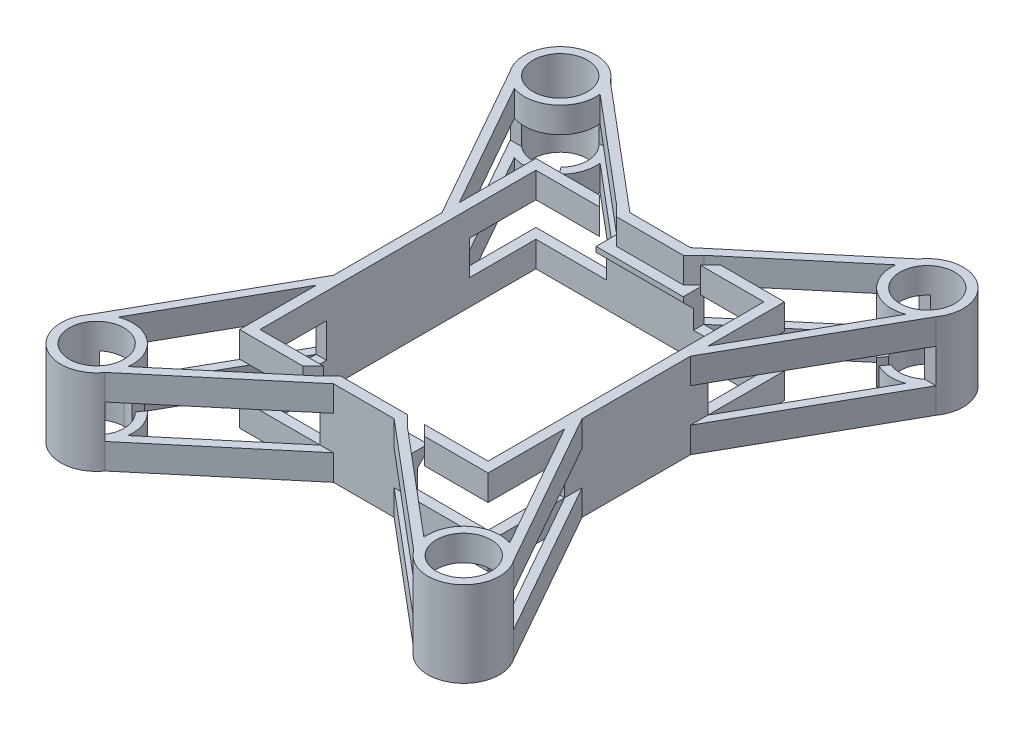
SolidWorks part; units mm, degrees
ref_plane "Front Plane" through (0, 0, 0) normal (0, 0, 1) x (1, 0, 0)
ref_plane "Top Plane" through (0, 0, 0) normal (0, 1, 0) x (1, 0, 0)
ref_plane "Right Plane" through (0, 0, 0) normal (1, 0, 0) x (0, 0, -1)
sketch "Sketch1" plane through (0, 0, 0) normal (0, 1, 0) x (1, 0, 0)
  line L0 (-24.0396, 23.0747) -> (-14.5922, 23.0747)
  line L1 (-22.8396, 21.8747) -> (3.8604, 21.8747)
  line L2 (-22.8396, 21.8747) -> (-22.8396, -10.4253)
  line L3 (-22.8396, -10.4253) -> (3.8604, -10.4253)
  line L4 (3.8604, 21.8747) -> (3.8604, -10.4253)
  line L5 (5.0604, 23.0747) -> (5.0604, 14.1087)
  line L6 (-24.0396, -11.6253) -> (-14.5922, -11.6253)
  line L7 (-24.0396, 23.0747) -> (-24.0396, 14.1087)
  line L8 (-32.3963, 28.911) -> (-24.0396, 14.1087)
  line L9 (-26.8082, 33.3597) -> (-14.5922, 23.0747)
  line L10 (-34.4055, 30.4359) -> (-24.0396, 12.0747)
  line L11 (-27.5525, 35.2935) -> (-13.0396, 23.0747)
  line L12 (-33.5347, 30.9275) -> (-23.1688, 12.5663) construction
  line L13 (-28.1965, 34.5285) -> (-13.6836, 22.3097) construction
  line L14 (-24.0396, 12.0747) -> (-24.0396, -0.6253)
  line L15 (-24.0396, 23.0747) -> (-24.0396, -11.6253) construction
  line L16 (-13.0396, 23.0747) -> (-5.9396, 23.0747)
  line L17 (-24.0396, 23.0747) -> (5.0604, 23.0747) construction
  line L18 (-9.4896, 43.1002) -> (-9.4896, -24.274) construction
  line L19 (-35.8782, 5.7247) -> (17.7365, 5.7247) construction
  line L20 (8.5733, 35.2935) -> (-5.9396, 23.0747)
  line L21 (7.8291, 33.3597) -> (-4.3869, 23.0747)
  line L22 (15.4263, 30.4359) -> (5.0604, 12.0747)
  line L23 (13.4171, 28.911) -> (5.0604, 14.1087)
  line L24 (-27.5525, -23.8442) -> (-13.0396, -11.6253)
  line L25 (-26.8082, -21.9104) -> (-14.5922, -11.6253)
  line L26 (-34.4055, -18.9866) -> (-24.0396, -0.6253)
  line L27 (-32.3963, -17.4617) -> (-24.0396, -2.6594)
  line L28 (8.5733, -23.8442) -> (-5.9396, -11.6253)
  line L29 (7.8291, -21.9104) -> (-4.3869, -11.6253)
  line L30 (13.4171, -17.4617) -> (5.0604, -2.6594)
  line L31 (15.4263, -18.9866) -> (5.0604, -0.6253)
  line L32 (-4.3869, 23.0747) -> (5.0604, 23.0747)
  line L33 (5.0604, 12.0747) -> (5.0604, -0.6253)
  line L34 (5.0604, 23.0747) -> (5.0604, -11.6253) construction
  line L35 (5.0604, -2.6594) -> (5.0604, -11.6253)
  line L36 (-4.3869, -11.6253) -> (5.0604, -11.6253)
  line L37 (-24.0396, -11.6253) -> (5.0604, -11.6253) construction
  line L38 (-13.0396, -11.6253) -> (-5.9396, -11.6253)
  line L39 (-24.0396, -2.6594) -> (-24.0396, -11.6253)
  circle A0 centre (-30.979, 32.8647) radius 3.2
  arc A1 (-27.5525, 35.2935) -> (-34.4055, 30.4359) centre (-30.979, 32.8647) ccw
  circle A2 centre (-30.979, 32.8647) radius 4.2 construction
  arc A3 (-32.3963, 28.911) -> (-26.8082, 33.3597) centre (-30.979, 32.8647) ccw
  arc A4 (13.4171, 28.911) -> (7.8291, 33.3597) centre (11.9998, 32.8647) cw
  arc A5 (8.5733, 35.2935) -> (15.4263, 30.4359) centre (11.9998, 32.8647) cw
  circle A6 centre (11.9998, 32.8647) radius 3.2
  arc A7 (-32.3963, -17.4617) -> (-26.8082, -21.9104) centre (-30.979, -21.4154) cw
  arc A8 (-27.5525, -23.8442) -> (-34.4055, -18.9866) centre (-30.979, -21.4154) cw
  circle A9 centre (-30.979, -21.4154) radius 3.2
  circle A10 centre (11.9998, -21.4154) radius 3.2
  arc A11 (8.5733, -23.8442) -> (15.4263, -18.9866) centre (11.9998, -21.4154) ccw
  arc A12 (13.4171, -17.4617) -> (7.8291, -21.9104) centre (11.9998, -21.4154) ccw
  point P8 (-13.0396, 23.0747)
  point P9 (-24.0396, 12.0747)
  point P17 (-30.979, 32.8647)
  point P42 (11.9998, 32.8647)
  point P54 (-30.979, -21.4154)
  point P65 (11.9998, -21.4154)
  dimension "D6" = 6.4
  dimension "D1" = 26.7
  dimension "D2" = 32.3
  dimension "D4" = 11
  dimension "D5" = 11
  dimension "D8" = 1
  dimension "D9" = 1
  dimension "D10" = 12
  dimension "D3" = 1.2
  dimension "D7" = 1
extrude "Boss-Extrude2" add sketch "Sketch1" along normal blind 10
ref_plane "Plane1" through (20, 0, 0) normal (1, 0, 0) x (0, 0, -1)
sketch "Sketch2" plane through (20, 0, 0) normal (1, 0, 0) x (0, 0, -1)
  line L1 (-18.9866, 10) -> (-18.9866, 0) construction
  line L2 (-0.6253, 10) -> (-0.6253, 0) construction
  line L3 (5.7247, -5.597) -> (5.7247, 19.988) construction
  line L5 (-18.9866, 5) -> (-18.9866, 7)
  line L6 (-18.9866, 7) -> (-0.6253, 7)
  line L7 (-0.6253, 5) -> (-0.6253, 7)
  line L9 (-18.9866, 5) -> (-18.9866, 3)
  line L10 (-18.9866, 3) -> (-0.6253, 3)
  line L11 (-0.6253, 5) -> (-0.6253, 3)
  line L12 (30.4359, 7) -> (12.0747, 7)
  line L13 (12.0747, 5) -> (12.0747, 7)
  line L15 (30.4359, 5) -> (30.4359, 7)
  line L16 (30.4359, 3) -> (12.0747, 3)
  line L17 (12.0747, 5) -> (12.0747, 3)
  line L19 (30.4359, 5) -> (30.4359, 3)
  dimension "D1" = 2
  dimension "D2" = 2
extrude "Cut-Extrude1" cut sketch "Sketch2" against normal through all
ref_plane "Plane2" through (0, 0, 30) normal (0, 0, 1) x (1, 0, 0)
sketch "Sketch3" plane through (0, 0, 30) normal (0, 0, 1) x (1, 0, 0)
  line L0 (-27.5525, 10) -> (-27.5525, 0) construction
  line L1 (-27.5525, 7) -> (8.5733, 7)
  line L2 (-27.5525, 7) -> (-27.5525, 3)
  line L3 (-27.5525, 3) -> (8.5733, 3)
  line L4 (8.5733, 7) -> (8.5733, 3)
  line L5 (8.5733, 10) -> (8.5733, 0) construction
extrude "Cut-Extrude2" cut sketch "Sketch3" against normal through all
sketch "Sketch4" plane through (-27.5525, 0, 0) normal (1, 0, 0) x (0, 0, -1)
  line L1 (-23.8442, 7) -> (-18.9866, 7)
  line L2 (-23.8442, 7) -> (-23.8442, 3)
  line L3 (-23.8442, 3) -> (-18.9866, 3)
  line L4 (-18.9866, 7) -> (-18.9866, 3)
extrude "Cut-Extrude3" cut sketch "Sketch4" against normal up to surface (1.343 mm away) up to face at (-30.979, 5, 18.601)
sketch "Sketch5" plane through (8.5733, 0, 0) normal (-1, 0, 0) x (0, 0, 1)
  line L1 (23.8442, 3) -> (18.9866, 3)
  line L2 (23.8442, 3) -> (23.8442, 7)
  line L3 (23.8442, 7) -> (18.9866, 7)
  line L4 (18.9866, 3) -> (18.9866, 7)
extrude "Cut-Extrude4" cut sketch "Sketch5" against normal up to surface (1.343 mm away) up to face at (11.9998, 5, 18.601)
sketch "Sketch6" plane through (-27.5525, 0, 0) normal (1, 0, 0) x (0, 0, -1)
  line L1 (35.2935, 3) -> (30.4359, 3)
  line L2 (35.2935, 3) -> (35.2935, 7)
  line L3 (35.2935, 7) -> (30.4359, 7)
  line L4 (30.4359, 3) -> (30.4359, 7)
extrude "Cut-Extrude5" cut sketch "Sketch6" against normal up to surface (1.343 mm away) up to face at (-30.979, 5, -30.0503)
sketch "Sketch7" plane through (8.5733, 0, 0) normal (-1, 0, 0) x (0, 0, 1)
  line L1 (-35.2935, 7) -> (-30.4359, 7)
  line L2 (-35.2935, 7) -> (-35.2935, 3)
  line L3 (-35.2935, 3) -> (-30.4359, 3)
  line L4 (-30.4359, 7) -> (-30.4359, 3)
extrude "Cut-Extrude6" cut sketch "Sketch7" against normal up to surface (1.343 mm away) up to face at (11.9998, 5, -30.0503)
sketch "Sketch8" plane through (0, 3, 0) normal (0, 1, 0) x (1, 0, 0)
  line L0 (3.8604, 21.8747) -> (-22.8396, 21.8747) construction
  line L1 (-14.5922, 23.0747) -> (-4.3869, 23.0747)
  line L2 (-14.5922, 23.0747) -> (-14.5922, 21.8747)
  line L3 (-14.5922, 21.8747) -> (-4.3869, 21.8747)
  line L4 (-4.3869, 23.0747) -> (-4.3869, 21.8747)
  line L5 (-22.8396, -10.4253) -> (3.8604, -10.4253) construction
  line L6 (-14.5922, -11.6253) -> (-4.3869, -11.6253)
  line L7 (-14.5922, -11.6253) -> (-14.5922, -10.4253)
  line L8 (-14.5922, -10.4253) -> (-4.3869, -10.4253)
  line L9 (-4.3869, -11.6253) -> (-4.3869, -10.4253)
  line L10 (-22.8396, 21.8747) -> (-22.8396, -10.4253) construction
  line L11 (-24.0396, 14.1087) -> (-22.8396, 14.1087)
  line L12 (-24.0396, 14.1087) -> (-24.0396, -2.6594)
  line L13 (-24.0396, -2.6594) -> (-22.8396, -2.6594)
  line L14 (-22.8396, 14.1087) -> (-22.8396, -2.6594)
  line L15 (3.8604, -10.4253) -> (3.8604, 21.8747) construction
  line L16 (5.0604, 14.1087) -> (3.8604, 14.1087)
  line L17 (5.0604, 14.1087) -> (5.0604, -2.6594)
  line L18 (5.0604, -2.6594) -> (3.8604, -2.6594)
  line L19 (3.8604, 14.1087) -> (3.8604, -2.6594)
extrude "Boss-Extrude3" add sketch "Sketch8" along normal up to surface (4 mm away) up to face at (-9.4896, 7, -5.7247)
sketch "Sketch9" plane through (0, 3, 0) normal (0, 1, 0) x (1, 0, 0)
  line L0 (-24.0396, 23.0747) -> (-29.1291, 30.2536) construction
  line L5 (-27.7174, 29.2998) -> (-28.6964, 28.6057)
  line L6 (-28.6964, 28.6057) -> (-30.7076, 31.4426)
  line L7 (-30.7076, 31.4426) -> (-29.7287, 32.1367)
  line L8 (-29.7287, 32.1367) -> (-27.7174, 29.2998)
  line L9 (-9.4896, 29.3) -> (-9.4896, -17.593) construction
  line L10 (-33.6155, 5.8535) -> (14.1538, 5.8535) construction
  line L11 (11.7285, 31.4426) -> (10.7495, 32.1367)
  line L12 (9.7172, 28.6057) -> (11.7285, 31.4426)
  line L13 (8.7383, 29.2998) -> (9.7172, 28.6057)
  line L14 (10.7495, 32.1367) -> (8.7383, 29.2998)
  line L15 (9.7172, -16.8987) -> (11.7285, -19.7356)
  line L16 (8.7383, -17.5927) -> (9.7172, -16.8987)
  line L17 (10.7495, -20.4296) -> (8.7383, -17.5927)
  line L18 (11.7285, -19.7356) -> (10.7495, -20.4296)
  line L19 (-30.7076, -19.7356) -> (-29.7287, -20.4296)
  line L20 (-28.6964, -16.8987) -> (-30.7076, -19.7356)
  line L21 (-27.7174, -17.5927) -> (-28.6964, -16.8987)
  line L22 (-29.7287, -20.4296) -> (-27.7174, -17.5927)
  circle A0 centre (-30.979, 32.8647) radius 3.2 construction
  point P8 (-28.2069, 28.9527)
  dimension "D1" = 1.2
  dimension "D2" = 1.2
extrude "Cut-Extrude7" cut sketch "Sketch9" against normal through all
sketch "Sketch10" plane through (0, 0, -21.8747) normal (0, 0, 1) x (1, 0, 0)
  line L0 (-4.3869, 7) -> (-4.3869, 3) construction
  line L1 (-14.5922, 7) -> (-4.3869, 7)
  line L2 (-14.5922, 7) -> (-14.5922, 6.4)
  line L3 (-14.5922, 6.4) -> (-4.3869, 6.4)
  line L4 (-4.3869, 7) -> (-4.3869, 6.4)
  dimension "D1" = 0.6
extrude "Boss-Extrude4" add sketch "Sketch10" along normal blind 1.2
chamfer "Chamfer1" distance 1.2 angle 45 1 edges at (-9.4896, 6.4, -21.8747)
sketch "Sketch12" plane through (0, 0, 10.4253) normal (0, 0, -1) x (-1, 0, 0)
  line L0 (14.5922, 7) -> (14.5922, 3) construction
  line L1 (4.3869, 7) -> (14.5922, 7)
  line L2 (4.3869, 7) -> (4.3869, 6.4)
  line L3 (4.3869, 6.4) -> (14.5922, 6.4)
  line L4 (14.5922, 7) -> (14.5922, 6.4)
  dimension "D1" = 0.6
extrude "Boss-Extrude5" add sketch "Sketch12" along normal blind 1.2
chamfer "Chamfer2" distance 1.2 angle 45 1 edges at (-9.4896, 6.4, 10.4253)
sketch "Sketch13" plane through (0, 10, 0) normal (0, 1, 0) x (1, 0, 0)
  line L0 (-14.5922, 23.0747) -> (-13.3922, 21.8747)
  line L1 (3.8604, 21.8747) -> (-22.8396, 21.8747) construction
  line L2 (-13.3922, 21.8747) -> (-15.394, 21.8747)
  line L3 (-15.394, 21.8747) -> (-16.594, 23.0747)
  line L4 (-24.0396, 23.0747) -> (-14.5922, 23.0747) construction
  line L5 (-16.594, 23.0747) -> (-14.5922, 23.0747)
  line L6 (-9.4896, 29.4178) -> (-9.4896, -25.2103) construction
  line L7 (-3.5852, 21.8747) -> (-2.3852, 23.0747)
  line L8 (-5.5869, 21.8747) -> (-3.5852, 21.8747)
  line L9 (-4.3869, 23.0747) -> (-5.5869, 21.8747)
  line L10 (-2.3852, 23.0747) -> (-4.3869, 23.0747)
  line L11 (-40.52, 5.7247) -> (15.8013, 5.7247) construction
  line L12 (-5.5869, -10.4253) -> (-3.5852, -10.4253)
  line L13 (-4.3869, -11.6253) -> (-5.5869, -10.4253)
  line L14 (-2.3852, -11.6253) -> (-4.3869, -11.6253)
  line L15 (-3.5852, -10.4253) -> (-2.3852, -11.6253)
  line L16 (-15.394, -10.4253) -> (-16.594, -11.6253)
  line L17 (-13.3922, -10.4253) -> (-15.394, -10.4253)
  line L18 (-14.5922, -11.6253) -> (-13.3922, -10.4253)
  line L19 (-16.594, -11.6253) -> (-14.5922, -11.6253)
extrude "Cut-Extrude8" cut sketch "Sketch13" against normal up to surface (3 mm away) and the other way through all up to face at (-20.4905, 7, -19.686)
